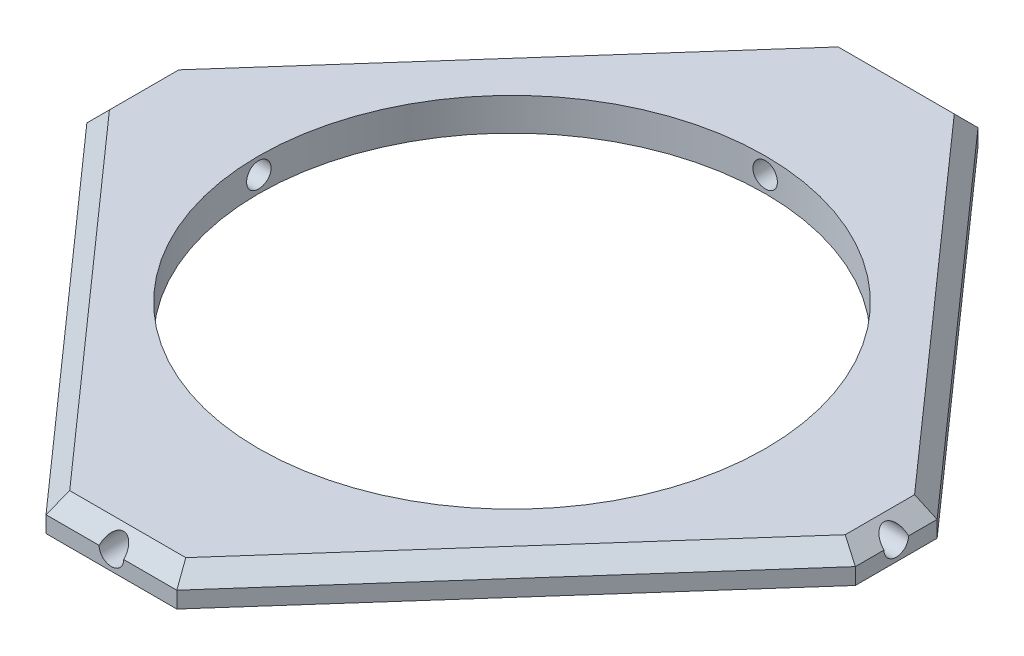
SolidWorks part; units mm, degrees
ref_plane "Front Plane" through (0, 0, 0) normal (0, 0, 1) x (1, 0, 0)
ref_plane "Top Plane" through (0, 0, 0) normal (0, 1, 0) x (1, 0, 0)
ref_plane "Right Plane" through (0, 0, 0) normal (1, 0, 0) x (0, 0, -1)
sketch "Sketch1" plane through (0, 0, 0) normal (0, 1, 0) x (1, 0, 0)
  line L0 (-235, 25) -> (-40, 245)
  line L1 (-40, -245) -> (40, -245)
  line L2 (-235, -25) -> (-235, 25)
  line L3 (-40, 245) -> (40, 245)
  line L4 (235, -25) -> (235, 25)
  line L6 (-40, 245) -> (40, -245) construction
  line L8 (-40, -245) -> (-40, 245) construction
  line L10 (40, -245) -> (40, 245) construction
  line L11 (-40, -245) -> (40, 245) construction
  line L13 (-235, -25) -> (235, -25) construction
  line L15 (-235, 25) -> (235, 25) construction
  line L17 (-235, -25) -> (235, 25) construction
  line L18 (-235, 25) -> (235, -25) construction
  line L19 (40, 245) -> (235, 25)
  line L20 (235, -25) -> (40, -245)
  line L21 (-40, -245) -> (-235, -25)
  point P0 (0, 0)
  point P6 (0, 0)
  point P11 (0, 0)
  dimension "D1" = 490
  dimension "D2" = 470
  dimension "D3" = 80
  dimension "D4" = 50
extrude "Boss-Extrude1" add sketch "Sketch1" along normal blind 20
sketch "Sketch2" plane through (0, 0, 245) normal (0, 0, 1) x (1, 0, 0)
  line L0 (-40, 20) -> (40, 0) construction
  line L1 (-40, 0) -> (40, 20) construction
  circle A0 centre (0, 10) radius 7.5
  dimension "D1" = 15
extrude "Cut-Extrude1" cut sketch "Sketch2" against normal through all contours A0
sketch "Sketch3" plane through (235, 0, 0) normal (1, 0, 0) x (0, 0, -1)
  line L0 (-25, 20) -> (25, 0) construction
  line L1 (-25, 0) -> (25, 20) construction
  circle A0 centre (0, 10) radius 7.5
  dimension "D1" = 15
extrude "Cut-Extrude2" cut sketch "Sketch3" against normal through all
chamfer "Chamfer1" distance 10 angle 45 8 edges at (137.5, 20, -135) (235, 20, 0) (137.5, 20, 135) (0, 20, 245) (-137.5, 20, 135) (-235, 20, 0) (-137.5, 20, -135) (0, 20, -245)
sketch "Sketch4" plane through (0, 20, 0) normal (0, 1, 0) x (1, 0, 0)
  circle A0 centre (0, 0) radius 155
  dimension "D1" = 310
extrude "Cut-Extrude3" cut sketch "Sketch4" against normal through all
ref_point "Point1"
